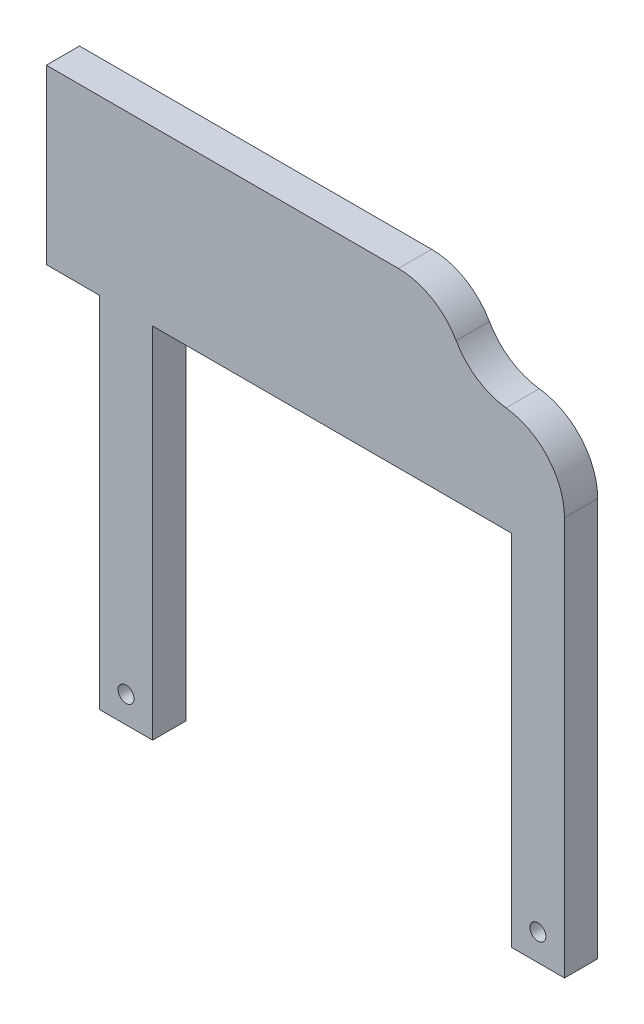
SolidWorks part; units mm, degrees
ref_plane "Plan de face" through (0, 0, 0) normal (0, 0, 1) x (1, 0, 0)
ref_plane "Plan de dessus" through (0, 0, 0) normal (0, 1, 0) x (1, 0, 0)
ref_plane "Plan de droite" through (0, 0, 0) normal (1, 0, 0) x (0, 0, -1)
sketch "Esquisse1" plane through (0, 0, 0) normal (0, 0, 1) x (1, 0, 0)
  line L36 (0, 0) -> (0, 54)
  line L41 (0, 140) -> (120, 140)
  line L42 (120, 140) -> (120, 130)
  line L43 (120, 130) -> (30, 130)
  line L44 (30, 130) -> (30, 80)
  line L45 (30, 80) -> (70, 80)
  line L46 (70, 80) -> (70, 0)
  line L47 (70, 0) -> (62, 0)
  line L48 (62, 0) -> (62, 54)
  line L49 (62, 54) -> (8, 54)
  line L50 (0, 0) -> (8, 0)
  line L51 (8, 0) -> (8, 54)
  line L52 (0, 80) -> (-8, 80)
  line L53 (-8, 80) -> (-8, 54)
  line L54 (-8, 54) -> (0, 54)
  line L55 (0, 80) -> (0, 140)
  dimension "D2" = 8
  dimension "D3" = 54
  dimension "D4" = 8
  dimension "D5" = 10
  dimension "D6" = 140
  dimension "D7" = 8
  dimension "D8" = 120
  dimension "D10" = 90
  dimension "D11" = 50
  dimension "D12" = 54
extrude "Boss.-Extru.1" add sketch "Esquisse1" along normal blind 5
sketch "Esquisse2" plane through (0, 0, 5) normal (0, 0, 1) x (1, 0, 0)
  line L0 (0, 0) -> (8, 0) construction
  line L1 (8, 0) -> (8, 54) construction
  line L2 (62, 0) -> (70, 0) construction
  line L3 (70, 0) -> (70, 80) construction
  circle A0 centre (4, 4) radius 1
  circle A1 centre (66, 4) radius 1
  dimension "D1" = 4
  dimension "D3" = 2
  dimension "D6" = 2
  dimension "D2" = 4
  dimension "D4" = 4
  dimension "D5" = 4
fillet "Congé1" [suppressed] radius 10
fillet "Congé2" radius 25 1 edges at (30, 130, 2.5)
sketch "Esquisse5" plane through (0, 0, 5) normal (0, 0, 1) x (1, 0, 0)
  line L1 (70, 80) -> (55, 80)
  line L2 (70, 80) -> (70, 70)
  line L3 (70, 70) -> (55, 70)
  line L4 (55, 80) -> (55, 70)
  dimension "D1" = 15
  dimension "D2" = 10
extrude "Enlèv. mat.-Extru.1" cut sketch "Esquisse5" against normal up to surface (5 mm away) up to face at (36.1072, 69.7752, 0)
sketch "Esquisse6" plane through (0, 0, 5) normal (0, 0, 1) x (1, 0, 0)
  line L0 (55, 130) -> (120, 130) construction
  line L1 (120, 140) -> (112, 140)
  line L2 (120, 140) -> (120, 130)
  line L3 (120, 130) -> (112, 130)
  line L4 (112, 140) -> (112, 130)
  dimension "D1" = 8
extrude "Enlèv. mat.-Extru.2" [suppressed] cut sketch "Esquisse6" against normal up to surface (5 mm away) up to face at (38.0959, 69.7988, 0)
fillet "Congé3" radius 10 2 edges at (70, 70, 2.5) (55, 80, 2.5)
fillet "Congé4" radius 10 1 edges at (55, 70, 2.5)
sketch "Esquisse7" plane through (0, 0, 5) normal (0, 0, 1) x (1, 0, 0)
  line L0 (0, 54) -> (0, 0) construction
  line L1 (120, 140) -> (0, 140)
  line L2 (120, 140) -> (120, 80)
  line L3 (120, 80) -> (0, 80)
  line L4 (0, 140) -> (0, 80)
  line L5 (45, 80) -> (30, 80) construction
extrude "Enlèv. mat.-Extru.3" cut sketch "Esquisse7" against normal up to surface (5 mm away) up to face at (38.7849, 69.6492, 0)
sketch "Esquisse8" [suppressed] plane through (0, 0, 5) normal (0, 0, 1) x (1, 0, 0)
  line L5 (0, 80) -> (-15, 80)
  line L6 (-15, 80) -> (-15, 54)
  line L7 (-15, 54) -> (0, 54)
  line L8 (0, 80) -> (0, 0) construction
  line L9 (8, 54) -> (62, 54) construction
  line L10 (0, 80) -> (0, 54)
  line L18 (45, 80) -> (0, 80)
  line L19 (0, 80) -> (0, 0)
  line L20 (0, 0) -> (8, 0)
  line L21 (8, 0) -> (8, 54)
  line L22 (8, 54) -> (62, 54)
  line L23 (62, 54) -> (62, 0)
  line L24 (62, 0) -> (70, 0)
  line L25 (70, 0) -> (70, 60)
  line L26 (45, 80) -> (0, 80)
  line L27 (0, 54) -> (0, 0)
  line L28 (0, 0) -> (8, 0)
  line L29 (8, 0) -> (8, 54)
  line L30 (8, 54) -> (62, 54)
  line L31 (62, 54) -> (62, 0)
  line L32 (62, 0) -> (70, 0)
  line L33 (70, 0) -> (70, 60)
  arc A3 (70, 60) -> (61.2017, 69.9275) centre (60, 60) ccw
  arc A4 (53.7017, 74.9275) -> (61.2017, 69.9275) centre (62.4034, 79.8551) ccw
  arc A5 (53.7017, 74.9275) -> (45, 80) centre (45, 70) ccw
  arc A6 (70, 60) -> (61.2017, 69.9275) centre (60, 60) ccw
  arc A7 (53.7017, 74.9275) -> (61.2017, 69.9275) centre (62.4034, 79.8551) ccw
  arc A8 (53.7017, 74.9275) -> (45, 80) centre (45, 70) ccw
  dimension "D1" = 15
  dimension "D2" = 0
extrude "Enlèv. mat.-Extru.5" cut sketch "Esquisse2" against normal blind 10
hole_wizard "Dégagement M21" positions "Esquisse3" profile "Esquisse4" hole size "M2" standard "ISO" end condition through all
sketch "Esquisse3" plane through (0, 0, 5) normal (0, 0, 1) x (1, 0, 0)
  point P0 (4, 4)
  point P3 (66, 4)
sketch "Esquisse4" plane through (4, 4, 5) normal (1, 0, 0) x (0, -1, 0)
  line L0 (0, 0) -> (0, 5)
  line L1 (0, 5) -> (1.2, 5)
  line L2 (1.2, 5) -> (1.2, 0)
  line L5 (1.2, 0) -> (0, 0)
  line L11 (0, -6.35) -> (0, 107.95) construction
  dimension "Diamètre du perçage jusqu'au prochain" = 2.4
  dimension "Profondeur du perçage jusqu'au prochain" = 5
